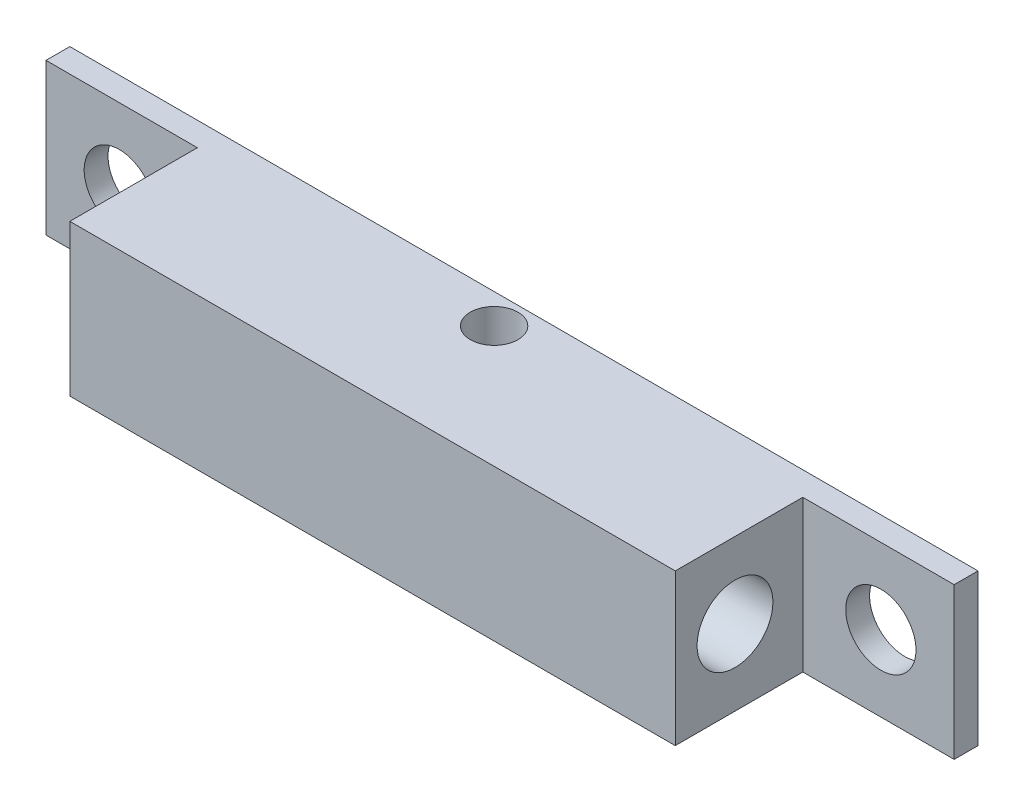
SolidWorks part; units mm, degrees
other "Markup1"
sketch "Sketch4" plane through (-6.35, -10, 15) normal (-0.3542, -0.9351, 0.0128) x (0.9346, -0.3545, -0.0309)
other "Markup2"
sketch "Sketch5" plane through (-6.35, 0, 6.35) normal (-0.9896, 0.1407, 0.0289) x (0.0558, 0.1909, 0.98)
material "6061 Alloy"
ref_plane "Front Plane" through (0, 0, 0) normal (0, 0, 1) x (1, 0, 0)
ref_plane "Top Plane" through (0, 0, 0) normal (0, 1, 0) x (1, 0, 0)
ref_plane "Right Plane" through (0, 0, 0) normal (1, 0, 0) x (0, 0, -1)
sketch "Sketch1" plane through (0, 0, 0) normal (0, 0, 1) x (1, 0, 0)
  line L1 (0, 0) -> (25.4, 0)
  line L2 (0, 0) -> (0, -6.35)
  line L3 (0, -6.35) -> (25.4, -6.35)
  line L4 (25.4, 0) -> (25.4, -6.35)
  line L5 (0, 0) -> (-6.35, 0)
  line L6 (0, 0) -> (0, -6.35)
  line L7 (0, -6.35) -> (-6.35, -6.35)
  line L8 (-6.35, 0) -> (-6.35, -6.35)
  line L9 (25.4, 0) -> (31.75, 0)
  line L10 (25.4, 0) -> (25.4, -6.35)
  line L11 (25.4, -6.35) -> (31.75, -6.35)
  line L12 (31.75, 0) -> (31.75, -6.35)
  circle A0 centre (-3.275, -3.175) radius 1.4732
  circle A1 centre (28.675, -3.175) radius 1.4732
  circle A2 centre (-3.275, -3.175) radius 2.3241 construction
  circle A3 centre (28.675, -3.175) radius 2.3241 construction
  point P19 (-6.35, -3.175)
  dimension "D1" = 2.9464
  dimension "D10" = 4.6482
  dimension "D11" = 4.6482
  dimension "D2" = 25.4
  dimension "D3" = 6.35
  dimension "D4" = 3.275
  dimension "D5" = 3.275
  dimension "D7" = 3.175
  dimension "D8" = 6.35
  dimension "D9" = 3.175
extrude "Boss-Extrude1" add sketch "Sketch1" along normal blind 1 contours L5 L8 L7 L2 A0 | L12 L9 L4 L11 A1 region at (-0.0898, -3.175, 0) region at (28.575, -0.0898, 0)
extrude "Boss-Extrude2" add sketch "Sketch1<3>" along normal blind 6.35 contours L4 L1 L2 L3 region at (12.7, -3.175, 0)
sketch "Sketch1<3>" plane through (0, 0, 0) normal (0, 0, 1) x (1, 0, 0) same geometry as "Sketch1"
sketch "Sketch2" plane through (0, 0, 0) normal (-1, 0, 0) x (0, 0, 1)
  line L1 (3.8448, 0) -> (3.8448, -6.35) construction
  line L2 (6.35, 0) -> (1, 0) construction
  line L3 (6.35, -6.35) -> (1, -6.35) construction
  line L4 (1, 0) -> (1, -6.35) construction
  circle A0 centre (3.8448, -3.175) radius 1.591
  dimension "D1" = 3.182
  dimension "D2" = 2.8448
  dimension "D3" = 0
  dimension "D4" = 3.175
extrude "Cut-Extrude1" cut sketch "Sketch2" against normal up to surface (25.4 mm away) up to face at (25.4, -3.175, 3.675)
sketch "Sketch3" plane through (0, 0, 0) normal (0, 1, 0) x (1, 0, 0)
  line L0 (0, -6.35) -> (0, -1) construction
  line L2 (-6.35, 0) -> (31.75, 0) construction
  circle A0 centre (12.7, -1.25) radius 1
  dimension "D1" = 2
  dimension "D2" = 12.7
  dimension "D3" = 1.25
extrude "Cut-Extrude2" cut sketch "Sketch3" against normal up to surface (6.35 mm away) contours A0 up to face at (12.7, -6.35, 2.0875)
equation "\"D4@Sketch1\"=(\"D3@Sketch1\")/2+0.1"
equation "\"D5@Sketch1\"=\"D4@Sketch1\""
equation "\"D7@Sketch1\"=\"D8@Sketch1\"/2"
equation "\"D9@Sketch1\"=\"D8@Sketch1\"/2"
